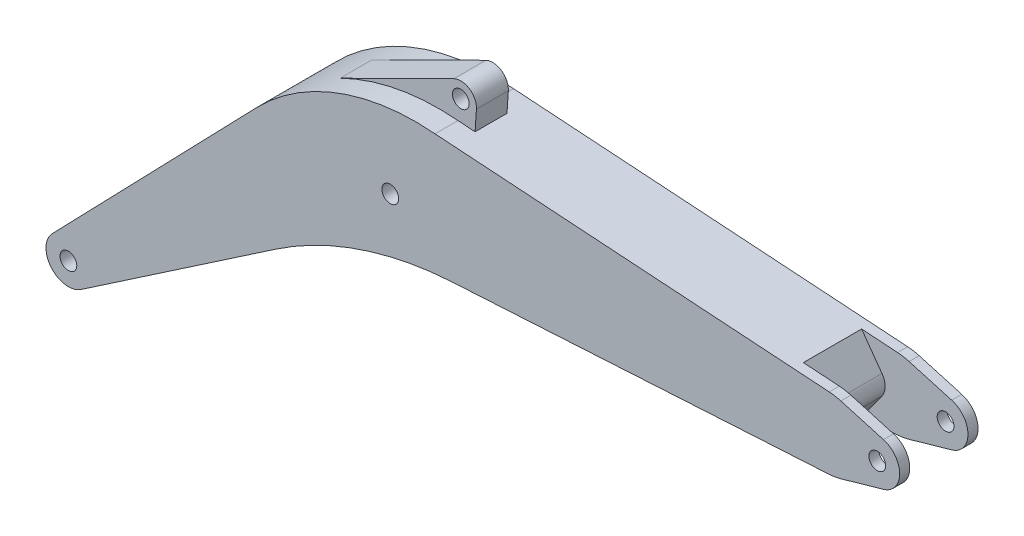
SolidWorks part; units mm, degrees
ref_plane "前视基准面" through (0, 0, 0) normal (0, 0, 1) x (1, 0, 0)
ref_plane "上视基准面" through (0, 0, 0) normal (0, 1, 0) x (1, 0, 0)
ref_plane "右视基准面" through (0, 0, 0) normal (1, 0, 0) x (0, 0, -1)
sketch "草图1" plane through (0, 0, 0) normal (0, 0, 1) x (1, 0, 0)
  line L0 (84.9387, 100.9448) -> (169.1185, 46.9656) construction
  line L1 (163.6, 91.5) -> (232.0719, 95.4882)
  line L2 (232.0719, 95.4882) -> (240.6992, 97.954)
  line L3 (160.6, 112.9) -> (232.0719, 108.1118)
  line L4 (232.0719, 108.1118) -> (240.6992, 105.646)
  line L5 (128.7, 101) -> (92.2246, 63.2806)
  line L6 (97.3478, 57.1913) -> (132.1, 80.8)
  line L7 (95.1, 60.5) -> (239.6, 60.5) construction
  line L8 (239.6, 60.5) -> (239.6, 101.8) construction
  line L9 (239.6, 101.8) -> (95.1, 101.8) construction
  line L10 (95.1, 101.8) -> (95.1, 60.5) construction
  line L11 (152.6, 99.6031) -> (152.6, 60.5) construction
  line L12 (132.1, 80.8) -> (132.1, 60.5) construction
  line L13 (128.7, 101) -> (128.7, 60.5) construction
  line L14 (160.6, 112.9) -> (160.6, 60.5) construction
  line L16 (163.6, 91.5) -> (163.6, 60.5)
  arc A0 (128.7, 101) -> (160.6, 112.9) centre (157.1228, 73.5146) cw
  arc A1 (92.2246, 63.2806) -> (97.3478, 57.1913) centre (95.1, 60.5) ccw
  arc A2 (132.1, 80.8) -> (163.6, 91.5) centre (167.2357, 29.0799) cw
  arc A3 (240.6992, 105.646) -> (240.6992, 97.954) centre (239.6, 101.8) cw
  circle A4 centre (239.6, 101.8) radius 1.5
  circle A5 centre (152.6, 99.6031) radius 1.5
  circle A6 centre (95.1, 60.5) radius 1.5
  dimension "D2" = 4
  dimension "D3" = 3
  dimension "D4" = 4
  dimension "D1" = 100
  dimension "D6" = 33.6
  dimension "D7" = 31
  dimension "D8" = 40.5
  dimension "D10" = 95.1
  dimension "D11" = 60.5
  dimension "D12" = 144.5
  dimension "D13" = 41.3
  dimension "D14" = 3.4
  dimension "D15" = 20.3
  dimension "D16" = 20.5
  dimension "D17" = 8
  dimension "D18" = 3
  dimension "D19" = 52.4
extrude "凸台-拉伸1" add sketch "草图1" along normal blind 7 and the other way blind 7 contours A3 L4 L3 A0 L5 A1 L6 A2 L1 L2 A6 A5 A4 region at (163.6972, 95.3089, 0)
fillet "圆角1" radius 10 2 edges at (232.0719, 95.4882, 0) (232.0719, 108.1118, 0)
sketch "草图3" plane through (0, 0, 0) normal (0, 0, 1) x (1, 0, 0)
  line L0 (160.6, 112.9) -> (231.0129, 108.1827) construction
  line L1 (163.6514, 112.6956) -> (163.8937, 116.3128)
  line L3 (160.6, 112.9) -> (232.0719, 108.1118) construction
  line L4 (159.8555, 119.0082) -> (139.5495, 108.9333)
  line L10 (163.6, 91.5) -> (230.9683, 95.4239)
  line L11 (233.1349, 95.792) -> (240.6992, 97.954)
  line L12 (240.6992, 105.646) -> (233.0925, 107.8201)
  line L13 (231.0129, 108.1827) -> (160.6, 112.9)
  line L14 (128.7, 101) -> (92.2246, 63.2806)
  line L15 (97.3478, 57.1913) -> (132.1, 80.8)
  line L16 (163.6, 91.5) -> (230.9683, 95.4239)
  line L17 (233.1349, 95.792) -> (240.6992, 97.954)
  line L18 (240.6992, 105.646) -> (233.0925, 107.8201)
  line L19 (231.0129, 108.1827) -> (160.6, 112.9)
  line L20 (128.7, 101) -> (92.2246, 63.2806)
  line L21 (97.3478, 57.1913) -> (132.1, 80.8)
  arc A0 (160.6, 112.9) -> (128.7, 101) centre (157.1228, 73.5146) ccw construction
  arc A1 (159.8555, 119.0082) -> (163.8937, 116.3128) centre (161.1, 116.5) cw
  circle A2 centre (161.1, 116.5) radius 1.5
  arc A9 (230.9683, 95.4239) -> (233.1349, 95.792) centre (230.3868, 105.407) ccw
  arc A10 (240.6992, 97.954) -> (240.6992, 105.646) centre (239.6, 101.8) ccw
  arc A11 (233.0925, 107.8201) -> (231.0129, 108.1827) centre (230.3444, 98.2051) ccw
  arc A12 (160.6, 112.9) -> (128.7, 101) centre (157.1228, 73.5146) ccw
  arc A13 (92.2246, 63.2806) -> (97.3478, 57.1913) centre (95.1, 60.5) ccw
  arc A14 (163.6, 91.5) -> (132.1, 80.8) centre (167.2357, 29.0799) ccw
  arc A15 (230.9683, 95.4239) -> (233.1349, 95.792) centre (230.3868, 105.407) ccw
  arc A16 (240.6992, 97.954) -> (240.6992, 105.646) centre (239.6, 101.8) ccw
  arc A17 (233.0925, 107.8201) -> (231.0129, 108.1827) centre (230.3444, 98.2051) ccw
  arc A18 (160.6, 112.9) -> (128.7, 101) centre (157.1228, 73.5146) ccw
  arc A19 (92.2246, 63.2806) -> (97.3478, 57.1913) centre (95.1, 60.5) ccw
  arc A20 (163.6, 91.5) -> (132.1, 80.8) centre (167.2357, 29.0799) ccw
  dimension "D1" = 3
  dimension "D5" = 2.8
  dimension "D3" = 56
  dimension "D4" = 66
  dimension "D2" = 0
extrude "凸台-拉伸2" add sketch "草图3" along normal blind 2.9 and the other way blind 2.8 contours L1 A1 L4 A2 region at (156.7685, 114.8999, 0)
sketch "草图4" plane through (0, 0, 0) normal (0, 0, 1) x (1, 0, 0)
  line L0 (224.6, 108.6124) -> (228.2365, 103.5503)
  line L1 (160.6, 112.9) -> (232.0719, 108.1118) construction
  line L2 (228.2256, 100.0347) -> (224.6, 95.053)
  line L3 (163.6, 91.5) -> (232.0719, 95.4882) construction
  line L4 (239.6, 101.8) -> (224.6, 101.8) construction
  line L5 (224.6, 101.8) -> (224.6, 108.6124) construction
  line L6 (224.6, 101.8) -> (224.6, 95.053) construction
  line L10 (163.6, 91.5) -> (230.9683, 95.4239)
  line L11 (233.1349, 95.792) -> (240.6992, 97.954)
  line L12 (240.6992, 105.646) -> (233.0925, 107.8201)
  line L13 (231.0129, 108.1827) -> (160.6, 112.9)
  line L14 (128.7, 101) -> (92.2246, 63.2806)
  line L15 (97.3478, 57.1913) -> (132.1, 80.8)
  line L16 (163.6, 91.5) -> (230.9683, 95.4239)
  line L17 (233.1349, 95.792) -> (240.6992, 97.954)
  line L18 (240.6992, 105.646) -> (233.0925, 107.8201)
  line L19 (231.0129, 108.1827) -> (160.6, 112.9)
  line L20 (128.7, 101) -> (92.2246, 63.2806)
  line L21 (97.3478, 57.1913) -> (132.1, 80.8)
  arc A0 (228.2365, 103.5503) -> (228.2256, 100.0347) centre (225.8, 101.8) cw
  arc A7 (230.9683, 95.4239) -> (233.1349, 95.792) centre (230.3868, 105.407) ccw
  arc A8 (240.6992, 97.954) -> (240.6992, 105.646) centre (239.6, 101.8) ccw
  arc A9 (233.0925, 107.8201) -> (231.0129, 108.1827) centre (230.3444, 98.2051) ccw
  arc A10 (160.6, 112.9) -> (128.7, 101) centre (157.1228, 73.5146) ccw
  arc A11 (92.2246, 63.2806) -> (97.3478, 57.1913) centre (95.1, 60.5) ccw
  arc A12 (163.6, 91.5) -> (132.1, 80.8) centre (167.2357, 29.0799) ccw
  arc A13 (230.9683, 95.4239) -> (233.1349, 95.792) centre (230.3868, 105.407) ccw
  arc A14 (240.6992, 97.954) -> (240.6992, 105.646) centre (239.6, 101.8) ccw
  arc A15 (233.0925, 107.8201) -> (231.0129, 108.1827) centre (230.3444, 98.2051) ccw
  arc A16 (160.6, 112.9) -> (128.7, 101) centre (157.1228, 73.5146) ccw
  arc A17 (92.2246, 63.2806) -> (97.3478, 57.1913) centre (95.1, 60.5) ccw
  arc A18 (163.6, 91.5) -> (132.1, 80.8) centre (167.2357, 29.0799) ccw
  dimension "D2" = 3
  dimension "D3" = 15
  dimension "D4" = 1.2
  dimension "D1" = 0
extrude "切除-拉伸1" cut sketch "草图4" against normal blind 5.2 and the other way blind 5.2 contours L0 A0 L2 region at (234.0235, 101.8062, 0)
scale "Scale1" scale about centroid uniform scaling yes scale factor 1.5
